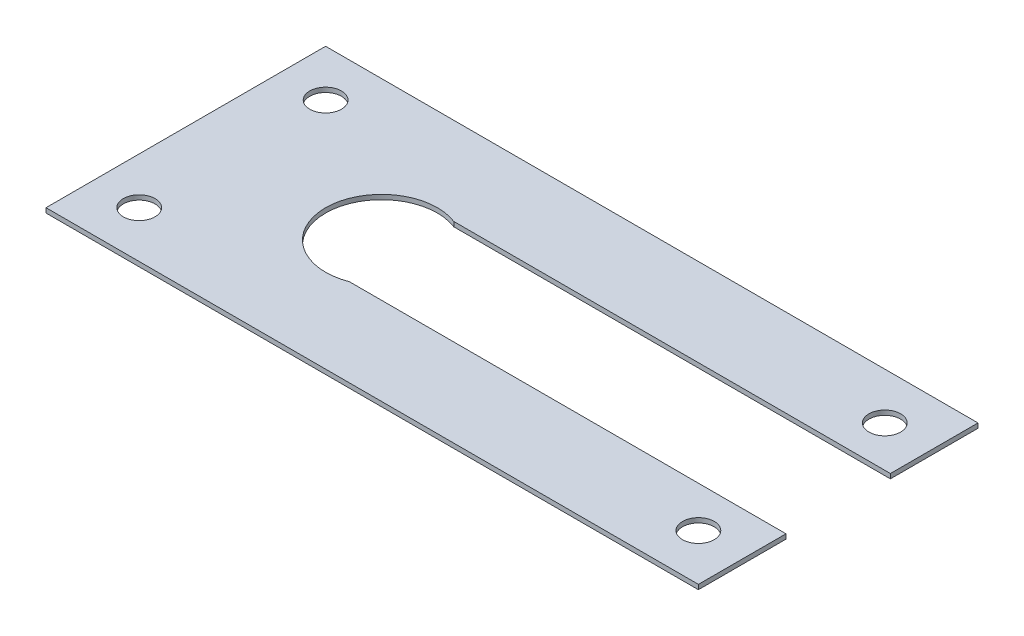
SolidWorks part; units mm, degrees
note: The reader was unsure of these and kept them because the rebuilt part matched: thickness of "Tôle de base pliée1", "Tôlerie3".
ref_plane "Plan de face" through (0, 0, 0) normal (0, 0, 1) x (1, 0, 0)
ref_plane "Plan de dessus" through (0, 0, 0) normal (0, 1, 0) x (1, 0, 0)
ref_plane "Plan de droite" through (0, 0, 0) normal (1, 0, 0) x (0, 0, -1)
sketch "Esquisse1" plane through (0, 0, 0) normal (0, 1, 0) x (1, 0, 0)
  line L0 (-0.275, 0) -> (0.275, 0) construction
  line L1 (-35, -15) -> (35, -15)
  line L2 (-35, -15) -> (-35, 15)
  line L3 (-35, 15) -> (35, 15)
  line L4 (35, -15) -> (35, -5.6)
  line L5 (-35, -15) -> (35, 15) construction
  line L6 (-35, 15) -> (35, -15) construction
  line L7 (-11.8459, 5.6) -> (35, 5.6)
  line L8 (-11.8459, -5.6) -> (35, -5.6)
  line L9 (35, 5.6) -> (35, 15)
  line L10 (0, -0.275) -> (0, 0.275) construction
  arc A0 (-11.8459, 5.6) -> (-11.8459, -5.6) centre (-14, 0) ccw
  circle A1 centre (30, 10) radius 1.7
  circle A3 centre (30, -10) radius 1.7
  circle A5 centre (-30, -10) radius 1.7
  circle A6 centre (-30, 10) radius 1.7
  point P0 (0, 0)
  dimension "D3" = 12
  dimension "D4" = 49
  dimension "D6" = 3.4
  dimension "D7" = 5
  dimension "D1" = 30
  dimension "D2" = 70
  dimension "D5" = 11.2
  dimension "D8" = 5
base flange "Tôle de base pliée1" sketch "Esquisse1" thickness 0.5 reverse thickness direction no parameters "D1"=0.7366
sketch "Esquisse13" plane through (0, 0, 0) normal (0, 0, 1) x (1, 0, 0)
  line L0 (-20, 0) -> (-20, -0.5) construction
sketch "Lignes de pliage3" [suppressed] plane through (0, 0, 0) normal (0, 1, 0) x (1, 0, 0)
sketch "Cube de visualisation3" [suppressed] plane through (0, 0, 0) normal (0, 1, 0) x (1, 0, 0)
sheet metal parameters "Tôlerie3" thickness 0.5 parameters "D1"=0.7366
flat pattern "Etat déplié3" [suppressed]
sketch "Lignes de pliage4" plane through (0, 0, 0) normal (0, 1, 0) x (1, 0, 0)
sketch3d "Cube de visualisation4" [suppressed]
  line L0 (49, -15, 0) -> (-21, -15, 0) construction
  line L1 (49, 15, 0) -> (-21, 15, 0) construction
  line L2 (49, -15, 0) -> (49, 15, 0) construction
  line L3 (-21, -15, 0) -> (-21, 15, 0) construction
